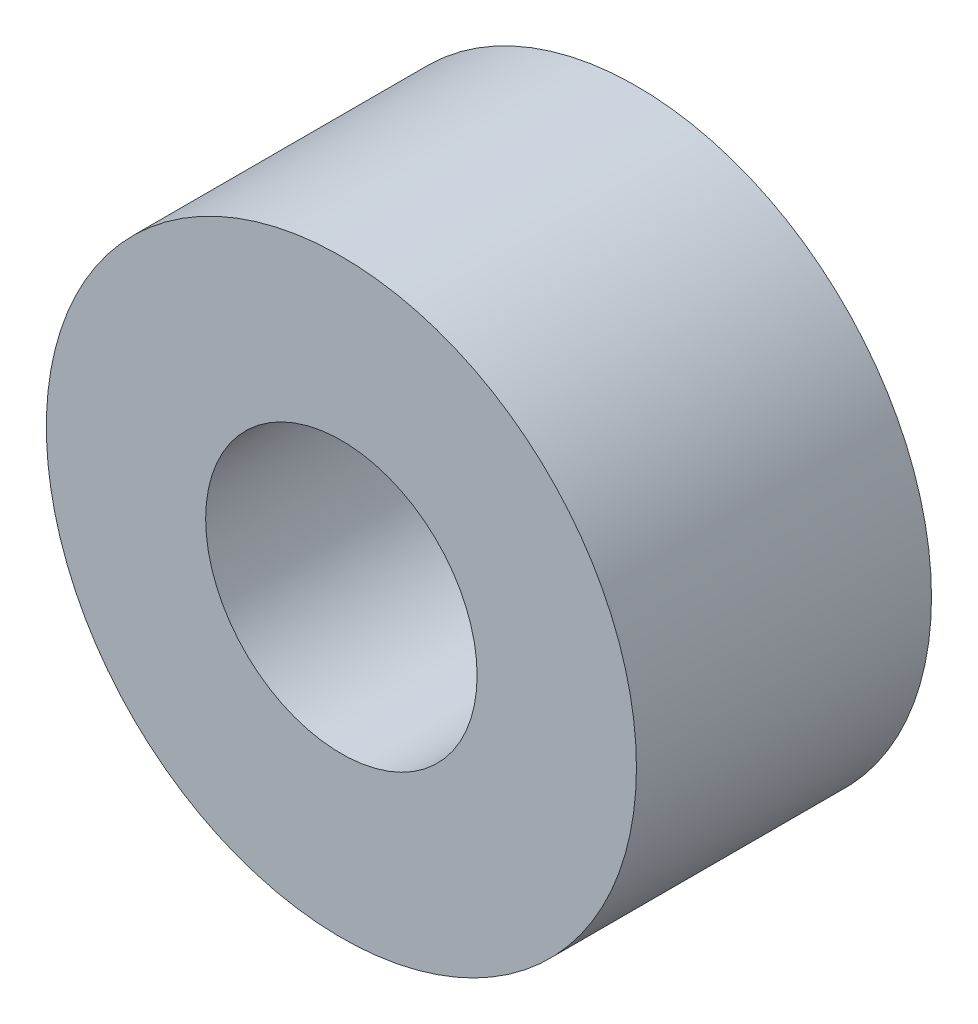
SolidWorks part; units mm, degrees
material "Nylon 6/10"
ref_plane "Front Plane" through (0, 0, 0) normal (0, 0, 1) x (1, 0, 0)
ref_plane "Top Plane" through (0, 0, 0) normal (0, 1, 0) x (1, 0, 0)
ref_plane "Right Plane" through (0, 0, 0) normal (1, 0, 0) x (0, 0, -1)
sketch "Sketch1" plane through (0, 0, 0) normal (0, 0, 1) x (1, 0, 0)
  circle A0 centre (0, 0) radius 3.175
  circle A1 centre (0, 0) radius 1.4605
  dimension "OD" = 6.35
  dimension "ID" = 2.921
extrude "Extrude1" add sketch "Sketch1" along normal mid plane 3.175
sketch "Sketch2" plane through (0, 0, 0) normal (1, 0, 0) x (0, 0, -1)
  line L0 (-1.5875, -1.4605) -> (1.5875, -1.4605) construction
  line L3 (1.5875, 1.4605) -> (-1.5875, 1.4605) construction
  line L5 (-1.5875, -1.4605) -> (1.5875, -1.4605)
  line L6 (1.5875, 1.4605) -> (-1.5875, 1.4605)
sketch "Sketch4" plane through (0, 0, 1.5875) normal (0, 0, 1) x (1, 0, 0)
  line L0 (0, 0) -> (-1.0327, 1.0327)
  line L1 (0, -3.4925) -> (0, 3.4925) construction
  circle A0 centre (0, 0) radius 1.4605 construction
  dimension "D1" = 45
